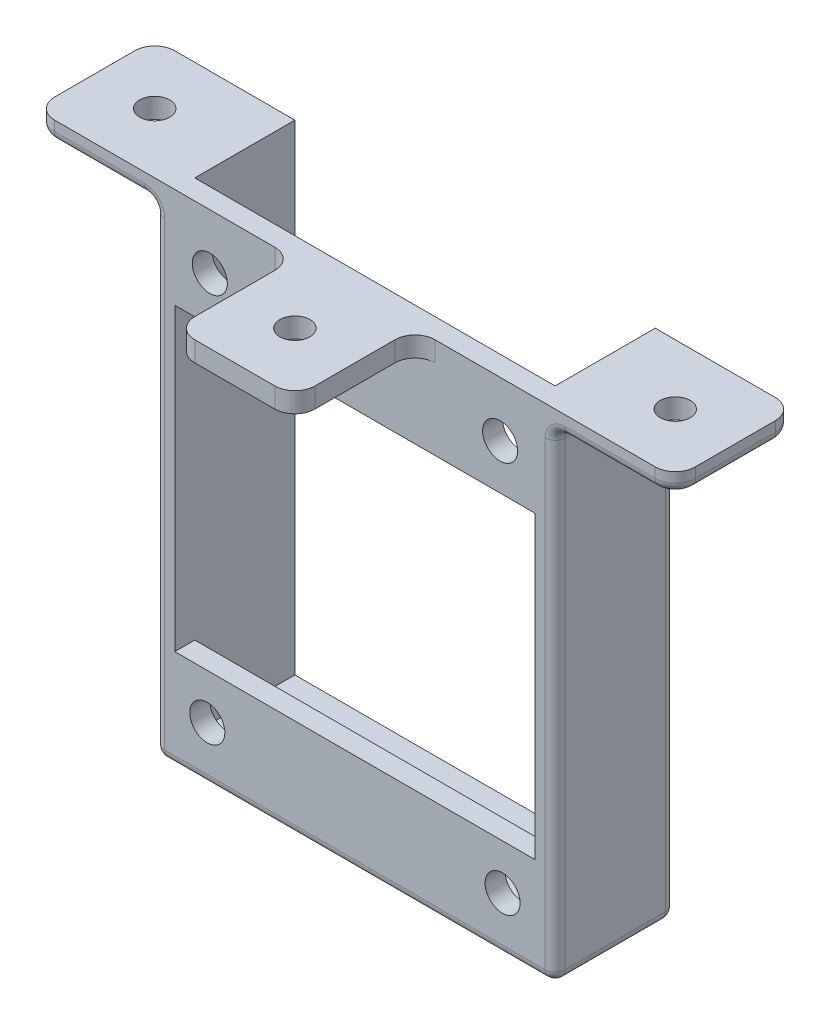
SolidWorks part; units mm, degrees
ref_plane "前视基准面" through (0, 0, 0) normal (0, 0, 1) x (1, 0, 0)
ref_plane "上视基准面" through (0, 0, 0) normal (0, 1, 0) x (1, 0, 0)
ref_plane "右视基准面" through (0, 0, 0) normal (1, 0, 0) x (0, 0, -1)
sketch "草图3" plane through (0, 0, 0) normal (0, 0, 1) x (1, 0, 0)
  line L0 (-20, 25) -> (20, 25)
  line L1 (-18, -23) -> (18, -23)
  line L2 (-18, -23) -> (-18, 23)
  line L3 (-18, 23) -> (18, 23)
  line L4 (18, -23) -> (18, 23)
  line L5 (-18, -23) -> (18, 23) construction
  line L6 (-18, 23) -> (18, -23) construction
  line L7 (20, -25) -> (20, 25)
  line L8 (-20, -25) -> (20, -25)
  line L9 (-20, -25) -> (-20, 25)
  point P0 (0, 0)
  dimension "D1" = 46
  dimension "D2" = 36
  dimension "D3" = 2
extrude "凸台-拉伸1" add sketch "草图3" along normal blind 12 contours L0 L7 L8 L9
sketch "草图5" plane through (0, 0, 0) normal (0, 0, -1) x (-1, 0, 0)
  line L0 (18, 23) -> (-18, 23)
  line L1 (-18, 23) -> (-18, -23)
  line L2 (-18, -23) -> (18, -23)
  line L3 (18, -23) -> (18, 23)
  line L4 (20, -25) -> (20, 25)
  line L5 (20, 25) -> (-20, 25)
  line L6 (-20, 25) -> (-20, -25)
  line L7 (-20, -25) -> (20, -25)
  line L8 (20, -25) -> (20, 25)
  line L9 (20, 25) -> (-20, 25)
  line L10 (-20, 25) -> (-20, -25)
  line L11 (-20, -25) -> (20, -25)
  dimension "D1" = 0
  dimension "D2" = 2
extrude "切除-拉伸2" cut sketch "草图5" against normal blind 10 contours L0 L1 L2 L3
sketch "草图6" plane through (0, 0, 10) normal (0, 0, -1) x (-1, 0, 0)
  line L4 (18, -23) -> (18, 23)
  line L5 (18, 23) -> (-18, 23)
  line L6 (-18, 23) -> (-18, -23)
  line L7 (-18, -23) -> (18, -23)
  line L8 (18, -23) -> (18, 23)
  line L9 (18, 23) -> (-18, 23)
  line L10 (-18, 23) -> (-18, -23)
  line L11 (-18, -23) -> (18, -23)
  dimension "D1" = 0
sketch "草图7" plane through (0, 0, 10) normal (0, 0, -1) x (-1, 0, 0)
  line L0 (0, 0) -> (0, 28.9981) construction
  line L1 (0, 0) -> (24.5091, 0) construction
  line L4 (18, -23) -> (18, 23)
  line L5 (18, 23) -> (-18, 23)
  line L6 (-18, 23) -> (-18, -23)
  line L7 (-18, -23) -> (18, -23)
  line L8 (18, -23) -> (18, 23)
  line L9 (18, 23) -> (-18, 23)
  line L10 (-18, 23) -> (-18, -23)
  line L11 (-18, -23) -> (18, -23)
  circle A0 centre (14.5, 19.5) radius 1.75
  circle A1 centre (14.75, -19.5) radius 1.75
  circle A2 centre (-14.75, -19.5) radius 1.75
  circle A3 centre (-14.5, 19.5) radius 1.75
  dimension "D2" = 3.5
  dimension "D3" = 3.5
  dimension "D4" = 3.5
  dimension "D1" = 0
extrude "切除-拉伸6" cut sketch "草图7" against normal blind 3 contours A0 | A3 | A2 | A1
sketch "草图11" plane through (20, 0, 0) normal (1, 0, 0) x (0, 0, -1)
  line L0 (0, -25) -> (0, 25) construction
  line L1 (0, 25) -> (-12, 25)
  line L2 (0, 25) -> (0, 23)
  line L3 (0, 23) -> (-12, 23)
  line L4 (-12, 25) -> (-12, 23)
  line L5 (-12, -25) -> (-12, 25) construction
  dimension "D1" = 2
extrude "凸台-拉伸2" add sketch "草图11" along normal blind 12
fillet "圆角1" radius 2 2 edges at (32, 24, 12) (32, 24, 0)
sketch "草图13" plane through (0, 23, 0) normal (0, -1, 0) x (1, 0, 0)
  line L0 (20, 12) -> (20, 0) construction
  line L1 (20, 12) -> (20, 0) construction
  line L2 (20, 6) -> (26, 6) construction
  circle A0 centre (26, 6) radius 1.5
  dimension "D1" = 3
  dimension "D2" = 6
extrude "切除-拉伸7" cut sketch "草图13" against normal blind 2
mirror "镜向1" about plane through (0, 0, 0) normal (1, 0, 0) of "切除-拉伸7", "凸台-拉伸2"
fillet "圆角4" radius 2 2 edges at (-32, 24, 0) (-32, 24, 12)
sketch "草图14" plane through (0, 0, 12) normal (0, 0, 1) x (1, 0, 0)
  line L0 (0, 25) -> (0, 17.4711) construction
  line L1 (-6, 25) -> (6, 25)
  line L2 (6, 25) -> (6, 23)
  line L3 (6, 23) -> (-6, 23)
  line L4 (-6, 25) -> (-6, 23)
  line L8 (30, 25) -> (-30, 25)
  line L9 (-30, 25) -> (-30, 23)
  line L10 (-30, 23) -> (-20, 23)
  line L11 (-20, 23) -> (-20, -25)
  line L12 (-20, -25) -> (20, -25)
  line L13 (20, -25) -> (20, 23)
  line L14 (20, 23) -> (30, 23)
  line L15 (30, 23) -> (30, 25)
  line L16 (30, 25) -> (-30, 25) construction
  line L17 (-30, 25) -> (-30, 23) construction
  line L18 (-30, 23) -> (-20, 23) construction
  line L19 (-20, 23) -> (-20, -25) construction
  line L20 (-20, -25) -> (20, -25) construction
  line L21 (20, -25) -> (20, 23) construction
  line L22 (20, 23) -> (30, 23) construction
  line L23 (30, 23) -> (30, 25) construction
  point P14 (0, 23)
  dimension "D1" = 0
  dimension "D2" = 6
  dimension "D3" = 2
extrude "凸台-拉伸3" add sketch "草图14" along normal blind 12
fillet "圆角5" radius 2 4 edges at (-6, 24, 12) (6, 24, 12) (-6, 24, 24) (6, 24, 24)
sketch "草图15" plane through (0, 23, 0) normal (0, -1, 0) x (1, 0, 0)
  line L0 (-8, 12) -> (8, 12) construction
  line L2 (-6, 22) -> (-6, 14) construction
  circle A0 centre (0, 18) radius 1.5
  dimension "D1" = 3
  dimension "D2" = 6
  dimension "D3" = 6
extrude "切除-拉伸8" cut sketch "草图15" against normal blind 12
fillet "圆角6" radius 1 6 edges at (-20, -25, 6) (0, -25, 12) (20, -25, 6) (0, -25, 0) (-20, 23, 6) (20, 23, 6)
fillet "圆角7" radius 1 22 edges at (-19.7071, -24.7071, 11.7071) (-19.7071, -24.7071, 0.2929) (-20, -1, 0) (-20.2929, 22.7071, 0) (-25.5, 23, 0) (-31.4142, 23, 0.5858) (-32, 23, 6) (-31.4142, 23, 11.4142) (-25.5, 23, 12) (-20.2929, 22.7071, 12) (19.7071, -24.7071, 0.2929) (19.7071, -24.7071, 11.7071) (20, -1, 12) (20.2929, 22.7071, 12) (25.5, 23, 12) (31.4142, 23, 11.4142) (32, 23, 6) (31.4142, 23, 0.5858) (25.5, 23, 0) (20.2929, 22.7071, 0) (-20, -1, 12) (20, -1, 0)
sketch "草图16" plane through (0, 23, 0) normal (0, -1, 0) x (-1, 0, 0)
  line L0 (18, -10) -> (18, 0)
  line L1 (18, 0) -> (-18, 0)
  line L2 (-18, 0) -> (-18, -10)
  line L3 (-18, -10) -> (18, -10)
extrude "切除-拉伸9" cut sketch "草图16" against normal through all
sketch "草图19" plane through (0, 0, 12) normal (0, 0, 1) x (1, 0, 0)
  line L1 (18, 14.9834) -> (-18, 14.9834)
  line L2 (18, 14.9834) -> (18, -14.9834)
  line L3 (18, -14.9834) -> (-18, -14.9834)
  line L4 (-18, 14.9834) -> (-18, -14.9834)
  line L5 (18, 14.9834) -> (-18, -14.9834) construction
  line L6 (18, -14.9834) -> (-18, 14.9834) construction
  point P0 (0, 0)
  dimension "D1" = 36
extrude "切除-拉伸10" cut sketch "草图19" against normal blind 3
sketch "草图20" plane through (0, 25, 0) normal (0, 1, 0) x (1, 0, 0)
  line L0 (0, 0) -> (0, -40.7697)
